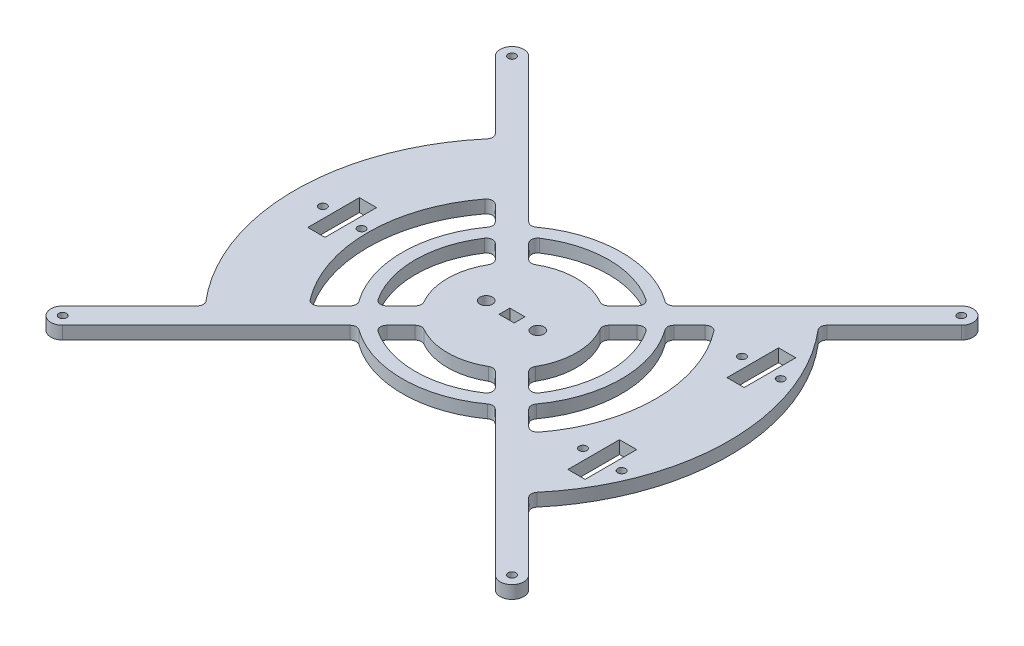
SolidWorks part; units mm, degrees
ref_plane "Front Plane" through (0, 0, 0) normal (0, 0, 1) x (1, 0, 0)
ref_plane "Top Plane" through (0, 0, 0) normal (0, 1, 0) x (1, 0, 0)
ref_plane "Right Plane" through (0, 0, 0) normal (1, 0, 0) x (0, 0, -1)
sketch "Sketch1" plane through (0, 0, 0) normal (0, 1, 0) x (1, 0, 0)
  line L0 (-110, -110) -> (110, 110) construction
  line L1 (-110, 110) -> (110, 110)
  line L2 (-110, 110) -> (-110, -110)
  line L3 (-110, -110) -> (110, -110)
  line L4 (110, 110) -> (110, -110)
  line L5 (-79, 110) -> (-79, -110) construction
  line L6 (75, 25) -> (75, -25) construction
  line L7 (0, 110) -> (0, -110) construction
  line L8 (-75, 0) -> (-70, 0) construction
  line L9 (0, 0) -> (70, 0) construction
  line L10 (-70, 0) -> (0, 0) construction
  line L11 (-83, 12) -> (-75, 12)
  line L12 (-83, 12) -> (-83, -12)
  line L13 (-83, -12) -> (-75, -12)
  line L14 (-75, 12) -> (-75, -12)
  line L15 (70, 0) -> (75, 0) construction
  line L16 (-83, 0) -> (-88, 0) construction
  line L17 (83, 37) -> (88, 37) construction
  line L18 (75, 49) -> (83, 49)
  line L19 (75, 49) -> (75, 25)
  line L20 (75, 25) -> (83, 25)
  line L21 (83, 49) -> (83, 25)
  line L22 (75, -25) -> (83, -25)
  line L23 (75, -25) -> (75, -49)
  line L24 (75, -49) -> (83, -49)
  line L25 (83, -25) -> (83, -49)
  line L26 (75, 37) -> (70, 37) construction
  line L27 (75, -37) -> (70, -37) construction
  line L28 (83, -37) -> (88, -37) construction
  circle A0 centre (-104.5, 104.5) radius 1.8
  circle A1 centre (104.5, 104.5) radius 1.8
  circle A2 centre (104.5, -104.5) radius 1.8
  circle A3 centre (-104.5, -104.5) radius 1.8
  circle A4 centre (-70, 0) radius 1.8
  circle A5 centre (-88, 0) radius 1.8
  circle A6 centre (88, 37) radius 1.8
  circle A7 centre (70, 37) radius 1.8
  circle A8 centre (88, -37) radius 1.8
  circle A9 centre (70, -37) radius 1.8
  point P8 (0, 0)
  point P26 (-79, 12)
  point P27 (0, 0)
  point P54 (0, 0)
  point P55 (72.4376, 0)
  point P56 (0, 0)
  dimension "D3" = 3.6
  dimension "D4" = 5.5
  dimension "D5" = 5.5
  dimension "D9" = 150
  dimension "D10" = 209
  dimension "D1" = 220
  dimension "D2" = 50
  dimension "D6" = 24
  dimension "D7" = 8
  dimension "D8" = 5
extrude "Boss-Extrude1" add sketch "Sketch1" along normal mid plane 6
sketch "Sketch2" plane through (0, -3, 0) normal (0, -1, 0) x (1, 0, 0)
  line L0 (-104.5, 104.5) -> (104.5, -104.5) construction
  line L1 (-110, 110) -> (110, 110)
  line L2 (-110, 110) -> (-110, -110)
  line L3 (-110, -110) -> (110, -110)
  line L4 (110, 110) -> (110, -110)
  line L5 (104.5, 104.5) -> (-104.5, -104.5) construction
  line L6 (-100.6109, 108.3891) -> (-108.3891, 100.6109)
  line L7 (-108.3891, 100.6109) -> (-24.7427, 16.9646)
  line L8 (-100.6109, 108.3891) -> (-16.9646, 24.7427)
  line L9 (-24.7427, 16.9646) -> (-16.9646, 24.7427)
  line L10 (-108.3891, -100.6109) -> (-100.6109, -108.3891)
  line L11 (-100.6109, -108.3891) -> (-16.9646, -24.7427)
  line L12 (-16.9646, -24.7427) -> (-24.7427, -16.9646)
  line L13 (-24.7427, -16.9646) -> (-108.3891, -100.6109)
  line L16 (100.6109, -108.3891) -> (108.3891, -100.6109)
  line L17 (108.3891, -100.6109) -> (24.7427, -16.9646)
  line L18 (24.7427, -16.9646) -> (16.9646, -24.7427)
  line L19 (16.9646, -24.7427) -> (100.6109, -108.3891)
  line L20 (100.6109, 108.3891) -> (108.3891, 100.6109)
  line L21 (108.3891, 100.6109) -> (24.7427, 16.9646)
  line L22 (24.7427, 16.9646) -> (16.9646, 24.7427)
  line L23 (16.9646, 24.7427) -> (100.6109, 108.3891)
  line L24 (0, 0) -> (-12, 0) construction
  line L25 (0, 0) -> (12, 0) construction
  circle A0 centre (-104.5, 104.5) radius 5.5
  circle A1 centre (0, 0) radius 101
  circle A2 centre (0, 0) radius 67
  circle A3 centre (-104.5, -104.5) radius 5.5
  circle A4 centre (0, 0) radius 30
  circle A5 centre (104.5, 104.5) radius 5.5
  circle A6 centre (104.5, -104.5) radius 5.5
  circle A7 centre (0, 0) radius 51
  circle A8 centre (0, 0) radius 45
  point P22 (-104.5, 104.5)
  point P27 (-104.5, -104.5)
  point P44 (104.5, -104.5)
  point P50 (104.5, 104.5)
  line M27 (-110, 110) -> (-110, -110)
  line M28 (-110, -110) -> (110, -110)
  line M29 (110, -110) -> (110, 110)
  line M30 (110, 110) -> (-110, 110)
  dimension "D1" = 11
  dimension "D4" = 11
  dimension "D6" = 60
  dimension "D7" = 6
  dimension "D8" = 90
  dimension "D10" = 134
  dimension "D11" = 202
  dimension "D2" = 11
  dimension "D5" = 11
  dimension "D9" = 12
extrude "Cut-Extrude1" cut sketch "Sketch2" against normal blind 10 contours A3 L13 A1 L7 A0 L2 | A6 L4 A5 L21 A1 L17 | A0 L1 M27 | A3 M27 M28 | A6 M28 M29 | A5 L4 M30 | A2 L23 A1 L8 | A5 L1 A0 L8 A1 L23 | A6 L19 A1 L11 A3 L3 | A2 L11 A1 L19 | A7 L23 A2 L8 | A7 L7 A2 L13 | A7 L11 A2 L19 | A7 L17 A2 L21 | L11 A8 L19 A4 | L7 A8 L13 A4 | L23 A8 L8 A4 | L17 A8 L21 A4 region at (-108.7715, -3, 108.7715) region at (0, -3, 107.8812) region at (-109.7771, -3, 102.3142) region at (108.7715, -3, 108.7715) region at (-108.7715, -3, -108.7715) region at (107.8812, -3, 0) region at (0, -3, 78.0573) region at (-102.3142, -3, -109.7771) region at (108.7715, -3, -108.7715) region at (0, -3, 54.7717) region at (-54.7717, -3, 0) region at (0, -3, -78.0573) region at (54.7717, -3, 0) region at (0, -3, 35.5609) region at (0, -3, -54.7717) region at (-35.5609, -3, 0) region at (35.5609, -3, 0) region at (0, -3, -35.5609)
fillet "Fillet1" radius 3 32 edges at (-75.2009, 0, -67.4227) (-75.2009, 0, 67.4227) (-51.1053, 0, -43.3272) (-51.1053, 0, 43.3272) (-39.7412, 0, 31.963) (-31.963, 0, -39.7412) (-39.7412, 0, -31.963) (-24.7427, 0, -16.9646) (-24.7427, 0, 16.9646) (-35.4703, 0, 27.6922) (-35.4703, 0, -27.6922) (-27.6922, 0, -35.4703) (27.6922, 0, -35.4703) (-16.9646, 0, -24.7427) (16.9646, 0, -24.7427) (31.963, 0, -39.7412) (75.2009, 0, 67.4227) (75.2009, 0, -67.4227) (51.1053, 0, 43.3272) (51.1053, 0, -43.3272) (39.7412, 0, -31.963) (24.7427, 0, -16.9646) (35.4703, 0, -27.6922) (24.7427, 0, 16.9646) (16.9646, 0, 24.7427) (-16.9646, 0, 24.7427) (35.4703, 0, 27.6922) (39.7412, 0, 31.963) (27.6922, 0, 35.4703) (31.963, 0, 39.7412) (-27.6922, 0, 35.4703) (-31.963, 0, 39.7412)
hole_wizard "M5 Clearance Hole1" positions "3DSketch1" profile "Sketch3" hole size "M5" standard "ANSI Metric" end condition through all
sketch3d "3DSketch1"
  point P0 (-12, -3, 0)
  point P3 (12, -3, 0)
sketch "Sketch3" plane through (-12, -3, 0) normal (1, 0, 0) x (0, 0, -1)
  line L0 (0, 0) -> (0, 6)
  line L1 (0, 6) -> (2.9, 6)
  line L2 (2.9, 6) -> (2.9, 0)
  line L5 (2.9, 0) -> (0, 0)
  line L11 (0, -6.35) -> (0, 107.95) construction
  dimension "Thru Hole Dia." = 5.8
  dimension "Thru Hole Depth" = 6
sketch "Sketch4" plane through (0, 3, 0) normal (0, 1, 0) x (1, 0, 0)
  line L0 (-12, 0) -> (-3.5, 0) construction
  line L1 (-3.5, -2.5) -> (3.5, -2.5)
  line L2 (-3.5, -2.5) -> (-3.5, 2.5)
  line L3 (-3.5, 2.5) -> (3.5, 2.5)
  line L4 (3.5, -2.5) -> (3.5, 2.5)
  line L5 (12, 0) -> (3.5, 0) construction
  dimension "D1" = 5
  dimension "D2" = 7
extrude "Cut-Extrude2" cut sketch "Sketch4" against normal through all
